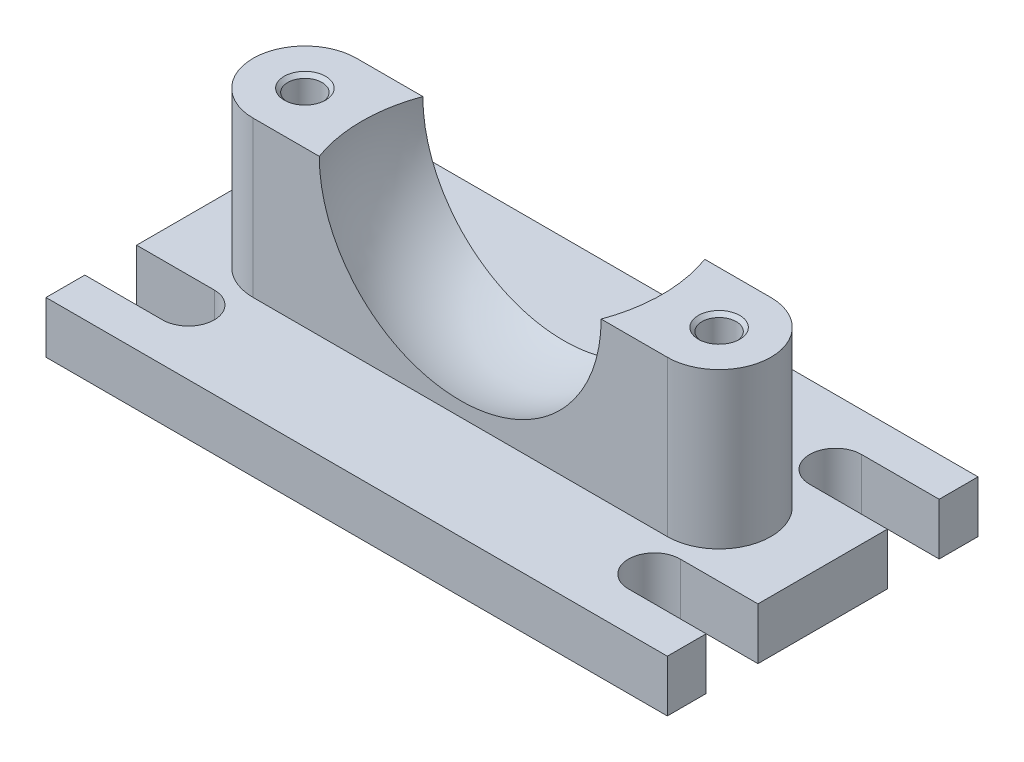
SolidWorks part; units mm, degrees
material "Сталь 40Х13 ГОСТ 5632-72"
ref_plane "Спереди" through (0, 0, 0) normal (0, 0, 1) x (1, 0, 0)
ref_plane "Сверху" through (0, 0, 0) normal (0, 1, 0) x (1, 0, 0)
ref_plane "Справа" through (0, 0, 0) normal (1, 0, 0) x (0, 0, -1)
sketch "Эскиз1" plane through (0, 0, 0) normal (0, 0, 1) x (1, 0, 0)
  line L0 (-35, 0) -> (35, 0)
  circle A0 centre (0, 0) radius 24
  circle A1 centre (0, 0) radius 35
  circle A2 centre (0, 0) radius 26
  dimension "D1" = 48
  dimension "D2" = 70
  dimension "D3" = 52
extrude "Бобышка-Вытянуть2" add sketch "Эскиз1" along normal mid plane 38 contours A2 L0 A1 | L0 A2 A0 region at (25, -0.5814, 0) region at (30.5, -0.7826, 0)
sketch "Эскиз2" plane through (0, 0, 0) normal (0, 1, 0) x (1, 0, 0)
  line L0 (-40, 0) -> (40, 0) construction
  line L1 (-40, 10) -> (40, 10)
  line L2 (-40, -10) -> (40, -10)
  arc A0 (-40, 10) -> (-40, -10) centre (-40, 0) ccw
  arc A1 (40, -10) -> (40, 10) centre (40, 0) ccw
  point P2 (0, 0)
  dimension "D1" = 40
  dimension "D2" = 10
extrude "Бобышка-Вытянуть5" add sketch "Эскиз2" against normal blind 40
extrude "Вырез-Вытянуть1" cut sketch "Эскиз1<4>" against normal up to surface and the other way up to surface contours A0 up to face at (0, -14.75, -19) other way up to face at (0, -14.75, 19)
sketch "Эскиз1<4>" plane through (0, 0, 0) normal (0, 0, 1) x (1, 0, 0) same geometry as "Эскиз1"
sketch "Эскиз4" plane through (0, -40, 0) normal (0, -1, 0) x (1, 0, 0)
  line L1 (-60, -30) -> (60, -30)
  line L2 (-60, -30) -> (-60, 30)
  line L3 (-60, 30) -> (60, 30)
  line L4 (60, -30) -> (60, 30)
  line L5 (-60, -30) -> (60, 30) construction
  line L6 (-60, 30) -> (60, -30) construction
  point P0 (0, 0)
  dimension "D1" = 120
  dimension "D2" = 60
extrude "Бобышка-Вытянуть6" add sketch "Эскиз4" against normal blind 10
fillet "Скругление2" radius 5 4 edges at (18.0278, -30, 14.5) (18.0278, -30, -14.5) (-18.0278, -30, -14.5) (-18.0278, -30, 14.5)
sketch "Эскиз5" plane through (0, -40, 0) normal (0, -1, 0) x (1, 0, 0)
  line L0 (-60, 0) -> (60, 0) construction
  line L1 (-60, 30) -> (-60, -30) construction
  line L2 (60, -30) -> (60, 30) construction
  line L3 (75, -17.5) -> (45, -17.5) construction
  line L4 (75, -22.5) -> (45, -22.5)
  line L5 (75, -12.5) -> (45, -12.5)
  arc A0 (75, -22.5) -> (75, -12.5) centre (75, -17.5) ccw
  arc A1 (45, -12.5) -> (45, -22.5) centre (45, -17.5) ccw
  point P8 (60, -17.5)
  dimension "D1" = 10
  dimension "D2" = 15
  dimension "D3" = 35
extrude "Вырез-Вытянуть2" cut sketch "Эскиз5" against normal through all
mirror "Зеркальное отражение1" about plane through (0, 0, 0) normal (0, 0, 1) of "Вырез-Вытянуть2"
mirror "Зеркальное отражение2" about plane through (0, 0, 0) normal (1, 0, 0) of "Зеркальное отражение1"
extrude "Вырез-Вытянуть3" cut sketch "Эскиз1<5>" against normal mid plane 24 contours L0 A2 A0 region at (25, -0.5814, 0)
sketch "Эскиз1<5>" plane through (0, 0, 0) normal (0, 0, 1) x (1, 0, 0) same geometry as "Эскиз1"
sketch "Эскиз6" plane through (0, 0, 0) normal (0, 0, 1) x (1, 0, 0)
  line L0 (0, -34) -> (0, -40)
  line L1 (60, -40) -> (-60, -40) construction
  line L2 (0, -40) -> (25, -40)
  line L3 (25, -40) -> (25, -34)
  line L4 (0, -34) -> (25, -34)
  dimension "D2" = 25
  dimension "D1" = 6
extrude "Вырез-Вытянуть4" cut sketch "Эскиз6" against normal mid plane 24 contours L3 L4 L0 L2
mirror "Зеркальное отражение3" about plane through (0, -34, -12) normal (-1, 0, 0) of "Вырез-Вытянуть4"
fillet "Скругление3" radius 4 2 edges at (25, -34, 0) (-25, -34, 0)
fillet "Скругление4" radius 2 14 edges at (-25, -39, 12) (-23.8284, -35.1716, 12) (25, -39, 12) (23.8284, -35.1716, 12) (-25, -39, -12) (-23.8284, -35.1716, -12) (25, -39, -12) (23.8284, -35.1716, -12) (0, -34, 12) (0, -34, -12) (0, -40, 12) (-25, -40, 0) (25, -40, 0) (0, -40, -12)
sketch "Эскиз7" plane through (0, 0, 0) normal (0, 1, 0) x (1, 0, 0)
  circle A0 centre (-40, 0) radius 3.3095
  circle A1 centre (40, 0) radius 3.3095
  dimension "D1" = 6.619
extrude "Вырез-Вытянуть5" cut sketch "Эскиз7" against normal blind 25
cosmetic thread "Условное изображение резьбы1" parameters "D2"=8
cosmetic thread "Условное изображение резьбы2" parameters "D2"=8
chamfer "Фаска1" distance 3.3 angle 45 2 edges at (40, -25, 3.3095) (-40, -25, 3.3095)
chamfer "Фаска2" distance 0.6905 angle 45 2 edges at (40, 0, 3.3095) (-40, 0, 3.3095)
sketch "Эскиз8" plane through (0, 0, 0) normal (0, 0, 1) x (1, 0, 0)
  line L0 (0, 0) -> (0, 43.0711) construction
  line L1 (0, 34) -> (0, -34)
  arc A0 (0, 34) -> (0, -34) centre (0, 0) ccw
  dimension "D1" = 68
revolve "Повернуть1" add sketch "Эскиз8" angle 360 about L0
sketch "Эскиз9" plane through (0, 0, 0) normal (0, 0, 1) x (1, 0, 0)
  line L0 (0, 0) -> (0, 43.0472) construction
  line L1 (0, 29) -> (0, -29)
  arc A0 (0, 29) -> (0, -29) centre (0, 0) ccw
  dimension "D1" = 58
revolve "Вырез-Повернуть1" cut sketch "Эскиз9" angle 360 about L0
sketch "Эскиз11" plane through (0, 0, 0) normal (0, 1, 0) x (1, 0, 0)
  line L1 (-60, 34) -> (60, 34)
  line L2 (-60, 34) -> (-60, -34)
  line L3 (-60, -34) -> (60, -34)
  line L4 (60, 34) -> (60, -34)
  line L5 (-60, 22.5) -> (-60, 30) construction
  line L6 (60, 12.5) -> (60, -12.5) construction
  arc A0 (28.1957, 19) -> (-28.1957, 19) centre (0, 0) ccw construction
  arc A1 (-28.1957, -19) -> (28.1957, -19) centre (0, 0) ccw construction
extrude "Вырез-Вытянуть8" cut sketch "Эскиз11" along normal through all
sketch "Эскиз12" plane through (0, 0, 19) normal (0, 0, 1) x (1, 0, 0)
  line L1 (-40, 0) -> (40, 0)
  line L2 (-40, 0) -> (-40, -30)
  line L3 (-40, -30) -> (40, -30)
  line L4 (40, 0) -> (40, -30)
extrude "Вырез-Вытянуть9" cut sketch "Эскиз12" against normal up to surface (9 mm away) and the other way through all up to face at (-34.5711, -16.7514, 10)
sketch "Эскиз13" plane through (0, 0, -10) normal (0, 0, -1) x (-1, 0, 0)
  line L1 (-40, 0) -> (40, 0)
  line L2 (-40, 0) -> (-40, -30)
  line L3 (-40, -30) -> (40, -30)
  line L4 (40, 0) -> (40, -30)
extrude "Вырез-Вытянуть10" cut sketch "Эскиз13" along normal through all
